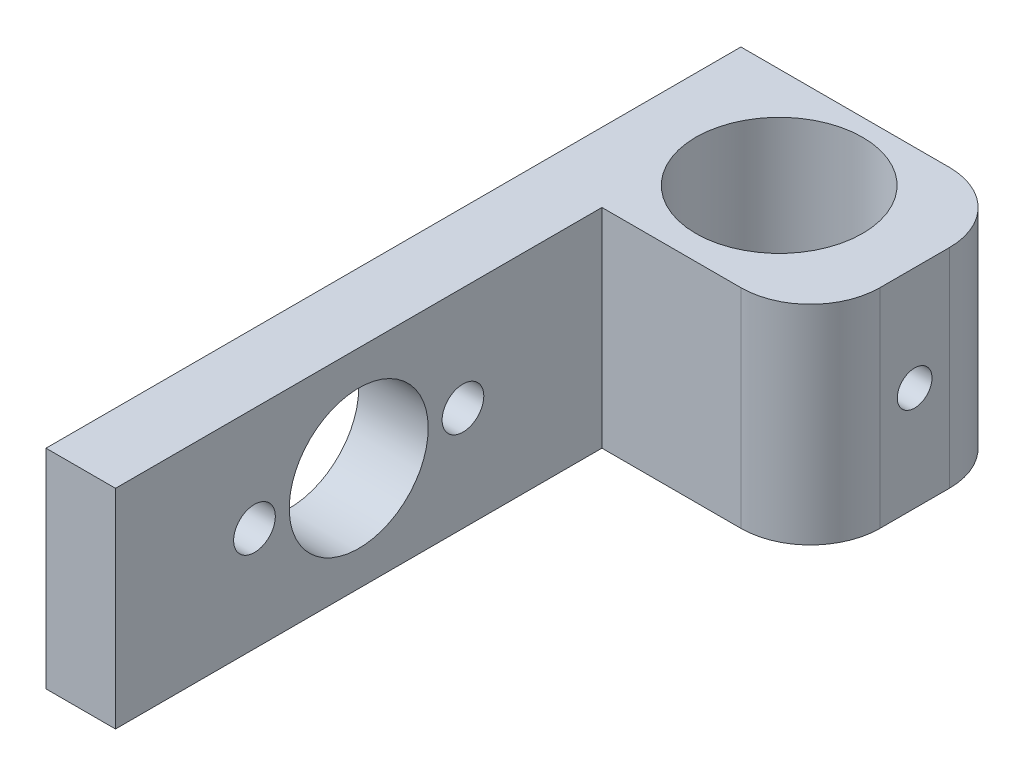
SolidWorks part; units mm, degrees
ref_plane "Front Plane" through (0, 0, 0) normal (0, 0, 1) x (1, 0, 0)
ref_plane "Top Plane" through (0, 0, 0) normal (0, 1, 0) x (1, 0, 0)
ref_plane "Right Plane" through (0, 0, 0) normal (1, 0, 0) x (0, 0, -1)
sketch "Sketch1" plane through (0, 0, 0) normal (1, 0, 0) x (0, 0, -1)
  line L1 (0, 0) -> (50, 0)
  line L2 (0, 0) -> (0, 15)
  line L3 (0, 15) -> (50, 15)
  line L4 (50, 0) -> (50, 15)
  circle A0 centre (10, 7.5) radius 1.5
  circle A1 centre (17.5, 7.5) radius 5
  circle A2 centre (25, 7.5) radius 1.5
  dimension "D3" = 10
  dimension "D4" = 3
  dimension "D5" = 3
  dimension "D1" = 7.5
  dimension "D2" = 7.5
  dimension "D6" = 10
  dimension "D7" = 7.5
  dimension "D8" = 7.5
  dimension "D9" = 7.5
  dimension "D10" = 7.5
  dimension "D11" = 50
extrude "Boss-Extrude1" add sketch "Sketch1" along normal mid plane 5
sketch "Sketch2" plane through (0, 15, 0) normal (0, 1, 0) x (1, 0, 0)
  line L0 (2.5, 50) -> (12.5, 50)
  line L1 (17.5, 45) -> (17.5, 40)
  line L2 (12.5, 35) -> (2.5, 35)
  line L3 (2.5, 50) -> (2.5, 0) construction
  line L4 (2.5, 39.4373) -> (2.5, 46.0705) construction
  line L5 (2.5, 35) -> (-2.5, 35)
  line L6 (-2.5, 50) -> (-2.5, 0) construction
  line L7 (-2.5, 35) -> (-2.5, 50)
  line L8 (-2.5, 50) -> (2.5, 50)
  line L9 (-2.5, 35) -> (12.5, 35)
  line L10 (-2.5, 50) -> (12.5, 50)
  line L11 (-2.5, 50) -> (-2.5, 35)
  line L12 (-2.5, 35) -> (12.5, 35)
  line L13 (17.5, 45) -> (17.5, 40)
  line L14 (-2.5, 50) -> (-2.5, 35)
  line L15 (-2.5, 50) -> (12.5, 50)
  line L16 (17.5, 45) -> (17.5, 40)
  circle A0 centre (7.5, 42.7539) radius 6
  arc A1 (17.5, 40) -> (12.5, 35) centre (12.5, 40) cw
  arc A2 (12.5, 50) -> (17.5, 45) centre (12.5, 45) cw
  dimension "D1" = 12
  dimension "D5" = 5
  dimension "D2" = 15
  dimension "D3" = 15
  dimension "D4" = 5
  dimension "D6" = 7.7539
extrude "Cut-Extrude1" cut sketch "Sketch2" against normal blind 1000 contours A0
sketch "Sketch5" plane through (0, 15, 0) normal (0, 1, 0) x (1, 0, 0)
  line L1 (-2.5, 50) -> (17.5, 50)
  line L2 (-2.5, 50) -> (-2.5, 35)
  line L3 (-2.5, 35) -> (17.5, 35)
  line L4 (17.5, 50) -> (17.5, 35)
  dimension "D1" = 15
  dimension "D2" = 20
extrude "Boss-Extrude2" add sketch "Sketch5" against normal blind 15
extrude "Cut-Extrude2" cut sketch "Sketch2<5>" against normal blind 15 contours A0
sketch "Sketch2<5>" plane through (0, 15, 0) normal (0, 1, 0) x (1, 0, 0) same geometry as "Sketch2"
fillet "Fillet1" radius 5 2 edges at (17.5, 7.5, -35) (17.5, 7.5, -50)
sketch "Sketch6" plane through (17.5, 0, 0) normal (1, 0, 0) x (0, 0, -1)
  line L0 (40, 0) -> (45, 0) construction
  line L1 (50, 15) -> (50, 0) construction
  circle A0 centre (42.5, 7.5) radius 1.25
  dimension "D1" = 7.5
  dimension "D2" = 2.5
  dimension "D3" = 7.5
extrude "Cut-Extrude3" cut sketch "Sketch6" against normal blind 15
